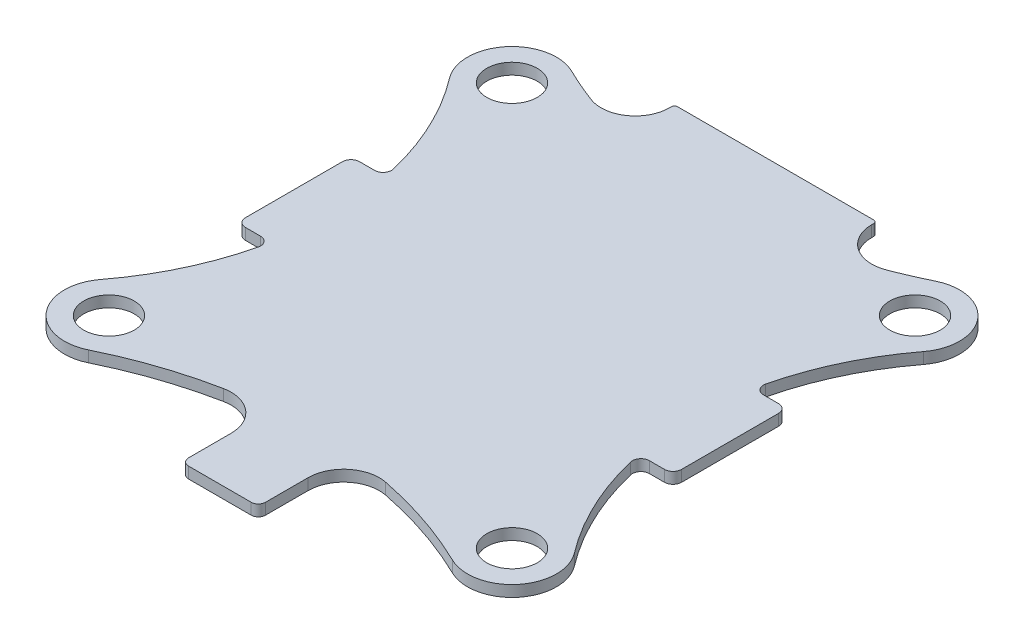
SolidWorks part; units mm, degrees
ref_plane "Front Plane" through (0, 0, 0) normal (0, 0, 1) x (1, 0, 0)
ref_plane "Top Plane" through (0, 0, 0) normal (0, 1, 0) x (1, 0, 0)
ref_plane "Right Plane" through (0, 0, 0) normal (1, 0, 0) x (0, 0, -1)
sketch "Sketch1" plane through (0, 0, 0) normal (0, 1, 0) x (1, 0, 0)
  line L0 (-17.9605, 17.9605) -> (17.9605, -17.9605) construction
  line L1 (-15.875, -17.78) -> (15.875, -17.78) construction
  line L2 (-15.875, -17.78) -> (-15.875, 17.78) construction
  line L3 (-15.875, 17.78) -> (15.875, 17.78) construction
  line L4 (15.875, -17.78) -> (15.875, 17.78) construction
  line L5 (-17.9605, -17.9605) -> (17.9605, 17.9605) construction
  line L6 (-20.7668, -15.1542) -> (-15.1542, -20.7668) construction
  line L7 (0, -17.78) -> (0, 17.78) construction
  line L8 (-15.875, 0) -> (15.875, 0) construction
  line L9 (20.7668, -15.1542) -> (15.1542, -20.7668) construction
  line L10 (-20.7668, 15.1542) -> (-15.1542, 20.7668) construction
  line L11 (20.7668, 15.1542) -> (15.1542, 20.7668) construction
  line L12 (-17.331, -5.08) -> (-18.669, -5.08)
  line L13 (-19.431, -4.318) -> (-19.431, 4.318)
  line L14 (-18.669, 5.08) -> (-17.331, 5.08)
  line L15 (18.669, 5.08) -> (17.331, 5.08)
  line L16 (19.431, -4.318) -> (19.431, 4.318)
  line L17 (-3.429, -21.6064) -> (-3.429, -25.4)
  line L18 (-2.794, -26.035) -> (2.794, -26.035)
  line L19 (3.429, -25.4) -> (3.429, -21.6064)
  line L20 (-9.017, 23.0455) -> (-9.017, 23.241)
  line L21 (-8.763, 23.495) -> (8.763, 23.495)
  line L22 (9.017, 23.241) -> (9.017, 23.0455)
  line L28 (17.331, -5.08) -> (18.669, -5.08)
  circle A0 centre (-17.9605, -17.9605) radius 3.9688 construction
  circle A1 centre (17.9605, -17.9605) radius 3.9688 construction
  circle A2 centre (17.9605, 17.9605) radius 3.9688 construction
  circle A3 centre (-17.9605, 17.9605) radius 3.9688 construction
  arc A4 (-21.1194, 15.5579) -> (-21.1194, -15.5579) centre (-41.5741, 0) cw construction
  arc A5 (-16.2197, 21.5271) -> (16.2197, 21.5271) centre (0, 54.7579) ccw construction
  arc A6 (-16.2197, -21.5271) -> (16.2197, -21.5271) centre (0, -54.7579) cw construction
  arc A7 (21.1194, 15.5579) -> (21.1194, -15.5579) centre (41.5741, 0) ccw construction
  arc A8 (-21.1194, 15.5579) -> (-16.2197, 21.5271) centre (-17.9605, 17.9605) cw
  arc A9 (16.2197, 21.5271) -> (21.1194, 15.5579) centre (17.9605, 17.9605) cw
  arc A10 (21.1194, -15.5579) -> (16.2197, -21.5271) centre (17.9605, -17.9605) cw
  arc A11 (-21.1194, -15.5579) -> (-16.2197, -21.5271) centre (-17.9605, -17.9605) ccw
  circle A12 centre (-17.9605, -17.9605) radius 2.25
  circle A13 centre (17.9605, -17.9605) radius 2.25
  circle A14 centre (17.9605, 17.9605) radius 2.25
  circle A15 centre (-17.9605, 17.9605) radius 2.25
  arc A16 (-21.1194, -15.5579) -> (-16.5902, -6.0205) centre (-41.5741, 0) ccw
  arc A17 (-17.331, -5.08) -> (-16.5902, -6.0205) centre (-17.331, -5.842) cw
  arc A18 (-21.1194, 15.5579) -> (-16.5902, 6.0205) centre (-41.5741, 0) cw
  arc A19 (-16.5902, 6.0205) -> (-17.331, 5.08) centre (-17.331, 5.842) cw
  arc A20 (-18.669, 5.08) -> (-19.431, 4.318) centre (-18.669, 4.318) ccw
  arc A21 (-19.431, -4.318) -> (-18.669, -5.08) centre (-18.669, -4.318) ccw
  arc A22 (16.5902, 6.0205) -> (17.331, 5.08) centre (17.331, 5.842) ccw
  arc A23 (21.1194, 15.5579) -> (16.5902, 6.0205) centre (41.5741, 0) ccw
  arc A24 (21.1194, -15.5579) -> (16.5902, -6.0205) centre (41.5741, 0) cw
  arc A25 (17.331, -5.08) -> (16.5902, -6.0205) centre (17.331, -5.842) ccw
  arc A26 (19.431, -4.318) -> (18.669, -5.08) centre (18.669, -4.318) cw
  arc A27 (18.669, 5.08) -> (19.431, 4.318) centre (18.669, 4.318) cw
  arc A28 (-16.2197, -21.5271) -> (-7.2243, -18.4926) centre (0, -54.7579) cw
  arc A29 (16.2197, -21.5271) -> (7.2243, -18.4926) centre (0, -54.7579) ccw
  arc A30 (-7.2243, -18.4926) -> (-3.429, -21.6064) centre (-6.604, -21.6064) cw
  arc A31 (7.2243, -18.4926) -> (3.429, -21.6064) centre (6.604, -21.6064) ccw
  arc A32 (-3.429, -25.4) -> (-2.794, -26.035) centre (-2.794, -25.4) ccw
  arc A33 (3.429, -25.4) -> (2.794, -26.035) centre (2.794, -25.4) cw
  arc A34 (-16.2197, 21.5271) -> (-13.1488, 20.1967) centre (0, 54.7579) ccw
  arc A35 (16.2197, 21.5271) -> (13.1488, 20.1967) centre (0, 54.7579) cw
  arc A36 (-9.017, 23.0455) -> (-13.1488, 20.1967) centre (-12.065, 23.0455) cw
  arc A37 (9.017, 23.0455) -> (13.1488, 20.1967) centre (12.065, 23.0455) ccw
  arc A38 (-8.763, 23.495) -> (-9.017, 23.241) centre (-8.763, 23.241) ccw
  arc A39 (8.763, 23.495) -> (9.017, 23.241) centre (8.763, 23.241) cw
  point P4 (0, 17.78)
  point P6 (15.875, 0)
  point P11 (0, 0)
  point P12 (0, 0)
  point P19 (-17.9605, -17.9605)
  point P60 (-19.431, 5.08)
  point P63 (-19.431, -5.08)
  point P72 (19.431, -5.08)
  point P73 (19.431, 5.08)
  point P82 (3.429, -17.9393)
  point P85 (-3.429, -26.035)
  point P88 (3.429, -26.035)
  point P95 (-9.017, 18.8962)
  point P98 (9.017, 18.8962)
  point P102 (-9.017, 23.495)
  point P105 (9.017, 23.495)
  dimension "D3" = 7.9375
  dimension "D8" = 0.762
  dimension "D9" = 0.762
  dimension "D10" = 0.762
  dimension "D11" = 0.762
  dimension "D14" = 3.175
  dimension "D15" = 3.175
  dimension "D16" = 0.635
  dimension "D17" = 0.635
  dimension "D20" = 3.048
  dimension "D21" = 3.048
  dimension "D22" = 4.5
  dimension "D23" = 0.254
  dimension "D24" = 0.254
  dimension "D1" = 31.75
  dimension "D2" = 35.56
  dimension "D4" = 50.8
  dimension "D5" = 3.556
  dimension "D6" = 5.08
  dimension "D7" = 5.08
  dimension "D12" = 6.858
  dimension "D13" = 8.255
  dimension "D18" = 5.715
  dimension "D19" = 18.034
extrude "Boss-Extrude2" add sketch "Sketch1" along normal blind 1 contours A12 | A13 | A14 | A15 | A28 A30 L17 A32 L18 A33 L19 A31 A29 A10 A24 A25 L28 A26 L16 A27 L15 A22 A23 A9 A35 A37 L22 A39 L21 A38 L20 A36 A34 A8 A18 A19 L14 A20 L13 A21 L12 A17 A16 A11 region at (-17.9605, 0, 17.9605) region at (17.9605, 0, 17.9605) region at (17.9605, 0, -17.9605) region at (-17.9605, 0, -17.9605)
